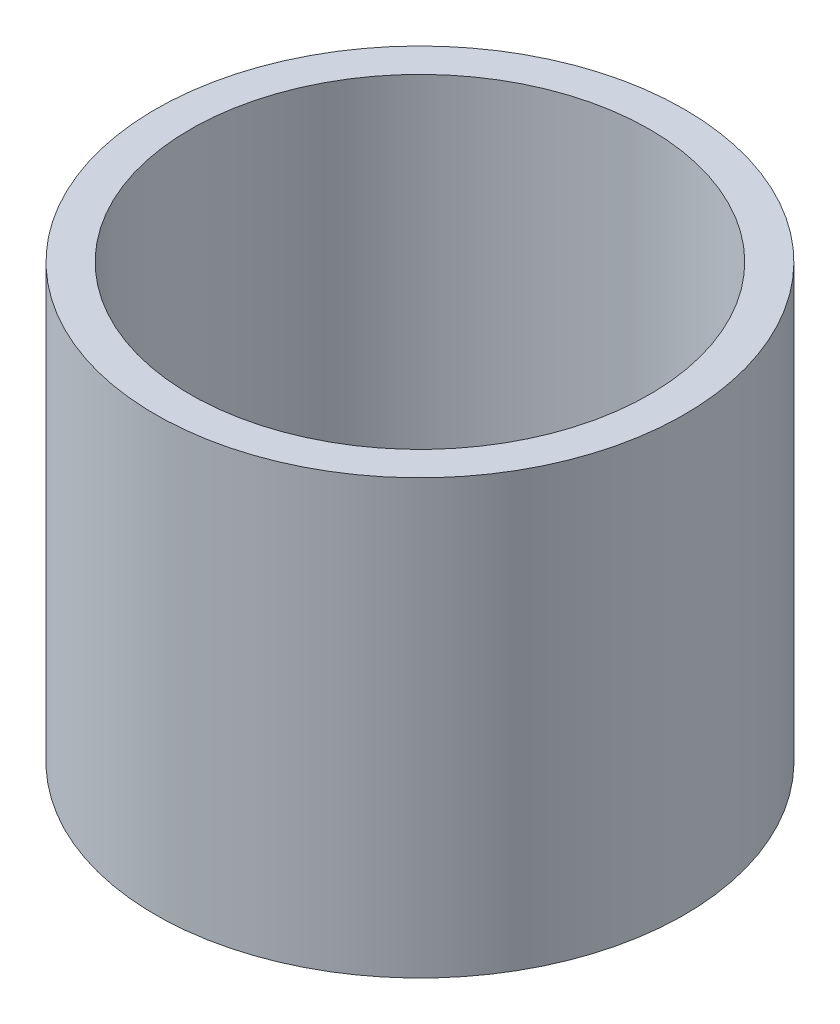
SolidWorks part; units mm, degrees
ref_plane "Front Plane" through (0, 0, 0) normal (0, 0, 1) x (1, 0, 0)
ref_plane "Top Plane" through (0, 0, 0) normal (0, 1, 0) x (1, 0, 0)
ref_plane "Right Plane" through (0, 0, 0) normal (1, 0, 0) x (0, 0, -1)
sketch "Sketch1" plane through (0, 0, 0) normal (0, 1, 0) x (1, 0, 0)
  circle A0 centre (0, 0) radius 30
  dimension "SLEEVE_OD" = 60
extrude "Boss-Extrude1" add sketch "Sketch1" along normal blind 49.1506
sketch "Sketch2" plane through (0, 0, 0) normal (0, 1, 0) x (1, 0, 0)
  circle A0 centre (0, 0) radius 26.0573
  dimension "BORE_D" = 52.1145
extrude "Cut-Extrude1" cut sketch "Sketch2" along normal through all
chamfer "Chamfer1" distance 2.1244 angle 45 rebuild error yes
